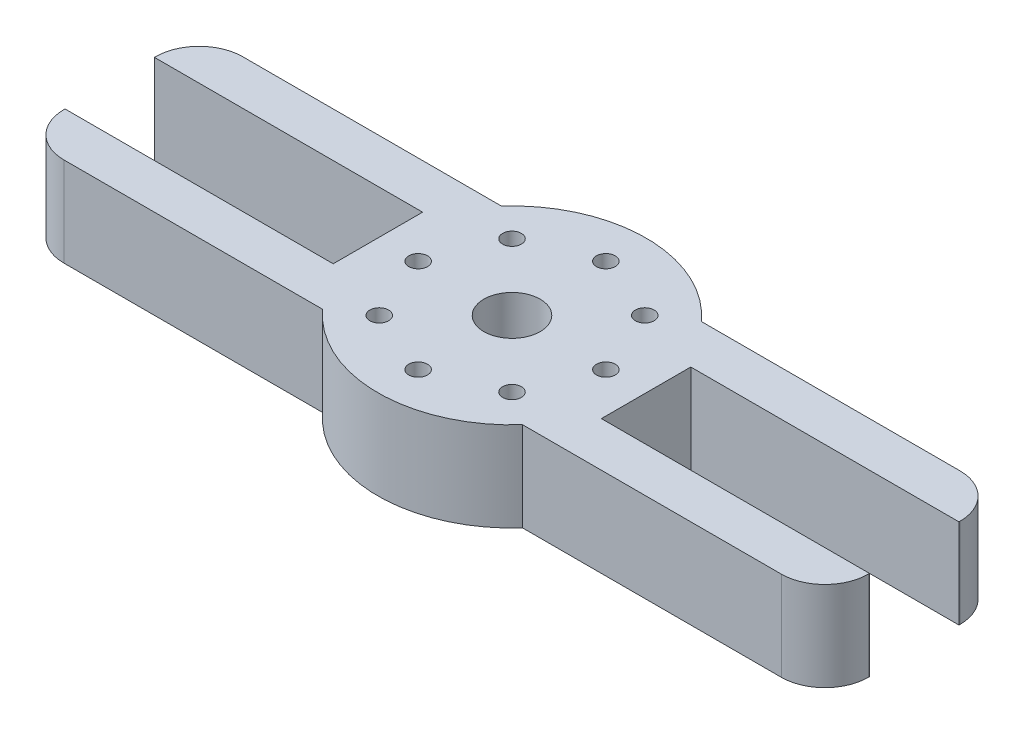
SolidWorks part; units mm, degrees
material "PTFE (general)"
ref_plane "Front Plane" through (0, 0, 0) normal (0, 0, 1) x (1, 0, 0)
ref_plane "Top Plane" through (0, 0, 0) normal (0, 1, 0) x (1, 0, 0)
ref_plane "Right Plane" through (0, 0, 0) normal (1, 0, 0) x (0, 0, -1)
sketch "Sketch1" plane through (0, 0, 0) normal (0, 1, 0) x (1, 0, 0)
  line L0 (22.3607, 20) -> (90, 20)
  line L1 (90, 20) -> (90, -20)
  line L2 (90, -20) -> (22.3607, -20)
  line L3 (0, -20) -> (0, 20)
  line L4 (0, 20) -> (0, 30)
  line L5 (0, -20) -> (0, -30)
  arc A0 (0, -30) -> (22.3607, -20) centre (0, 0) ccw
  arc A1 (22.3607, 20) -> (0, 30) centre (0, 0) ccw
  point P5 (0, 0)
  dimension "D1" = 60
  dimension "D2" = 90
  dimension "D3" = 40
extrude "Boss-Extrude1" add sketch "Sketch1" along normal blind 20
sketch "Sketch2" plane through (0, 20, 0) normal (0, 1, 0) x (1, 0, 0)
  line L0 (0, 6.3) -> (0, -6.3)
  line L1 (30, 10) -> (30, -10)
  line L2 (30, -10) -> (90, -10)
  line L3 (90, -10) -> (90, 10)
  line L4 (90, 10) -> (30, 10)
  line L6 (90, -20) -> (90, 20) construction
  arc A0 (0, -6.3) -> (0, 6.3) centre (0, 0) ccw
  point P1 (90, 0)
  point P8 (30, 0)
  dimension "D1" = 12.6
  dimension "D2" = 30
  dimension "D3" = 20
extrude "Cut-Extrude1" cut sketch "Sketch2" against normal up to surface (20 mm away) up to face at (37.8093, 0, 0)
fillet "Fillet1" radius 9.75 2 edges at (90, 10, 20) (90, 10, -20)
sketch "Sketch3" plane through (0, 0, -20) normal (0, 0, -1) x (-1, 0, 0)
  line L0 (0, 20) -> (0, 0) construction
  circle A0 centre (-40, 10) radius 2.5
  circle A1 centre (-50, 10) radius 2.5
  circle A2 centre (-60, 10) radius 2.5
  circle A3 centre (-70, 10) radius 2.5
  circle A4 centre (-80, 10) radius 2.5
  circle A5 centre (-90, 10) radius 2.5
  circle A6 centre (-100, 10) radius 2.5
  point P4 (0, 10)
  dimension "D2" = 5
  dimension "D1" = 40
  dimension "D3" = 7
extrude "Cut-Extrude2" [suppressed] cut sketch "Sketch3" against normal up to surface (40 mm away)
mirror "Mirror4" about plane through (0, 0, 0) normal (1, 0, 0) of "Boss-Extrude1", "Cut-Extrude1", "Fillet1", "Cut-Extrude2"
sketch "Sketch4" plane through (0, 20, 0) normal (0, 1, 0) x (1, 0, 0)
  circle A0 centre (21, 0) radius 2.1
  circle A1 centre (14.8492, -14.8492) radius 2.1
  circle A2 centre (0, -21) radius 2.1
  circle A3 centre (-14.8492, -14.8492) radius 2.1
  circle A4 centre (-21, 0) radius 2.1
  circle A5 centre (-14.8492, 14.8492) radius 2.1
  circle A6 centre (0, 21) radius 2.1
  circle A7 centre (14.8492, 14.8492) radius 2.1
  point P19 (0, 0)
  dimension "D2" = 4.2
  dimension "D1" = 21
  dimension "D3" = 8
extrude "Cut-Extrude3" cut sketch "Sketch4" against normal up to surface (20 mm away) up to face at (0, 0, 0)
sketch "Sketch5" plane through (0, 20, 0) normal (0, 1, 0) x (1, 0, 0)
  line L0 (0, 30) -> (0, -30) construction
  line L1 (-30, 0) -> (30, 0) construction
  line L2 (-30, 10) -> (-30, -10) construction
  line L3 (30, 10) -> (30, -10) construction
  arc A0 (22.3607, 20) -> (-22.3607, 20) centre (0, 0) ccw construction
  arc A1 (-22.3607, -20) -> (22.3607, -20) centre (0, 0) ccw construction
